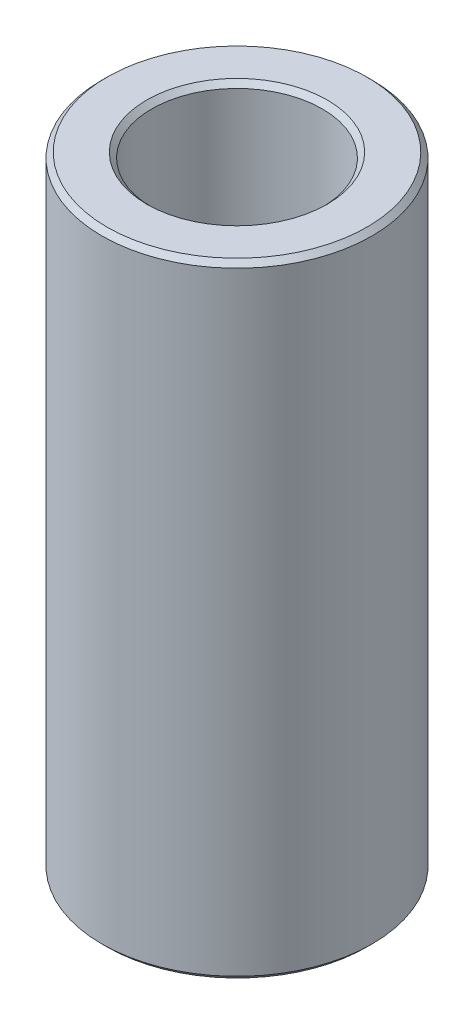
SolidWorks part; units mm, degrees
ref_plane "Front Plane" through (0, 0, 0) normal (0, 0, 1) x (1, 0, 0)
ref_plane "Top Plane" through (0, 0, 0) normal (0, 1, 0) x (1, 0, 0)
ref_plane "Right Plane" through (0, 0, 0) normal (1, 0, 0) x (0, 0, -1)
sketch "Sketch1" plane through (0, 0, 0) normal (0, 1, 0) x (1, 0, 0)
  circle A0 centre (0, 0) radius 55
  dimension "SLEEVE_OD" = 110
extrude "Boss-Extrude1" add sketch "Sketch1" along normal blind 253.867
sketch "Sketch2" plane through (0, 0, 0) normal (0, 1, 0) x (1, 0, 0)
  circle A0 centre (0, 0) radius 34.6973
  dimension "BORE_D" = 69.3945
extrude "Cut-Extrude1" cut sketch "Sketch2" along normal through all
chamfer "Chamfer1" distance 2.0738 angle 45 4 edges at (0, 253.867, 34.6973) (0, 0, 34.6973) (0, 0, 55) (0, 253.867, 55)
